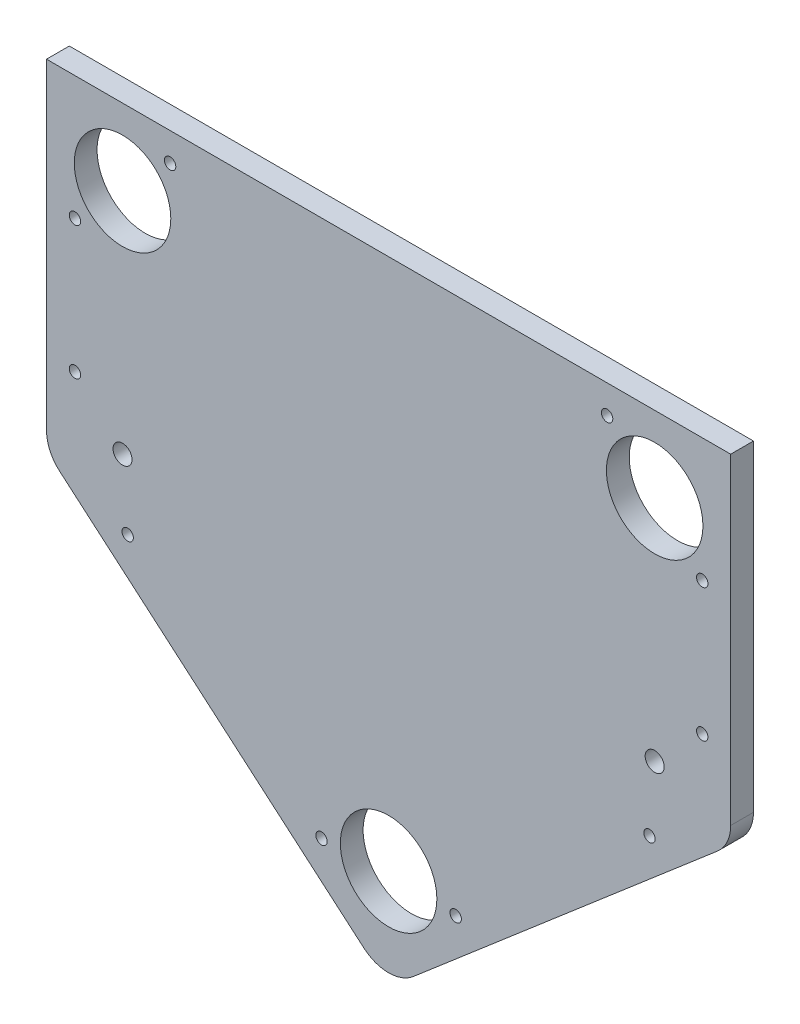
SolidWorks part; units mm, degrees
ref_plane "Front Plane" through (0, 0, 0) normal (0, 0, 1) x (1, 0, 0)
ref_plane "Top Plane" through (0, 0, 0) normal (0, 1, 0) x (1, 0, 0)
ref_plane "Right Plane" through (0, 0, 0) normal (1, 0, 0) x (0, 0, -1)
sketch "Sketch1" plane through (0, 0, 0) normal (0, 0, 1) x (1, 0, 0)
  line L0 (-70, 60) -> (70, 60) construction
  line L1 (-70, 0) -> (70, 0) construction
  line L2 (-82.5158, 47.4842) -> (-70, 60) construction
  line L3 (0, -60) -> (-70, 0) construction
  line L4 (0, -60) -> (-17.6479, -61.3575) construction
  line L5 (-68.6425, -17.6479) -> (-70, 0) construction
  line L6 (0, -60) -> (0, 60) construction
  line L7 (-90, 80) -> (90, 80)
  line L8 (90, 80) -> (90, -9.1987)
  line L9 (90, -9.1987) -> (0, -86.3416)
  line L10 (0, -86.3416) -> (-90, -9.1987)
  line L11 (-90, -9.1987) -> (-90, 80)
  circle A0 centre (-70, 60) radius 12.7
  circle A1 centre (70, 60) radius 12.7
  circle A2 centre (-70, 0) radius 2.5
  circle A3 centre (70, 0) radius 2.5
  circle A4 centre (0, -60) radius 12.7
  circle A5 centre (-82.5158, 47.4842) radius 1.5
  circle A6 centre (-57.4842, 72.5158) radius 1.5
  circle A7 centre (-82.5158, 12.5158) radius 1.5
  circle A8 centre (-68.6425, -17.6479) radius 1.5
  circle A9 centre (-17.6479, -61.3575) radius 1.5
  circle A10 centre (-70, 0) radius 12.7 construction
  circle A11 centre (70, 0) radius 12.7 construction
  circle A12 centre (-70, 0) radius 17.7 construction
  circle A13 centre (-70, 60) radius 17.7 construction
  circle A14 centre (0, -60) radius 17.7 construction
  circle A15 centre (17.6479, -61.3575) radius 1.5
  circle A16 centre (68.6425, -17.6479) radius 1.5
  circle A17 centre (82.5158, 12.5158) radius 1.5
  circle A18 centre (82.5158, 47.4842) radius 1.5
  circle A19 centre (57.4842, 72.5158) radius 1.5
  point P12 (0, 60)
  point P43 (0, 0)
  point P45 (0, 80)
  dimension "D1" = 25.4
  dimension "D2" = 5
  dimension "D5" = 3
  dimension "D3" = 60
  dimension "D4" = 60
  dimension "D6" = 5
  dimension "D7" = 135
  dimension "D8" = 45
  dimension "D9" = 140
  dimension "D10" = 45
  dimension "D11" = 20
  dimension "D12" = 20
  dimension "D13" = 20
  dimension "D14" = 20
  dimension "D15" = 20
extrude "Boss-Extrude1" add sketch "Sketch1" along normal blind 6
fillet "Fillet1" radius 10 3 edges at (-90, -9.1987, 3) (90, -9.1987, 3) (0, -86.3416, 3)
equation "\"carbon_fiber_tube_diam\"= 1in"
equation "\"clip_tube_diam\"= 6mm"
equation "\"D1@Sketch1\"=\"carbon_fiber_tube_diam\""
